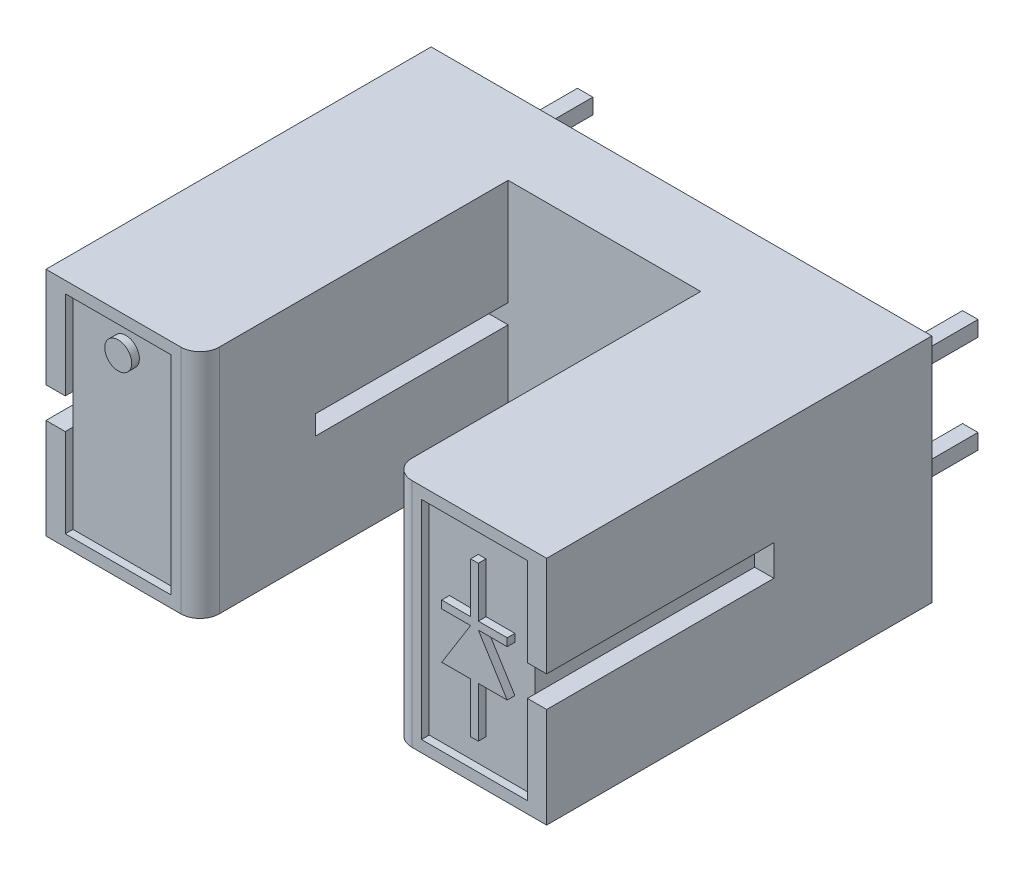
SolidWorks part; units mm, degrees
ref_plane "Front" through (0, 0, 0) normal (0, 0, 1) x (1, 0, 0)
ref_plane "Top" through (0, 0, 0) normal (0, 1, 0) x (1, 0, 0)
ref_plane "Right" through (0, 0, 0) normal (1, 0, 0) x (0, 0, -1)
sketch "Эскиз1" plane through (0, 0, 0) normal (0, 1, 0) x (1, 0, 0)
  line L0 (6.5, 0) -> (-6.5, 0)
  line L1 (6.5, 0) -> (6.5, -10)
  line L2 (6.5, -10) -> (2.5, -10)
  line L3 (2.5, -10) -> (2.5, -2)
  line L4 (2.5, -2) -> (-2.5, -2)
  line L5 (-2.5, -2) -> (-2.5, -10)
  line L6 (-2.5, -10) -> (-6.5, -10)
  line L8 (-6.5, 0) -> (-6.5, -10)
  line L9 (0, 0) -> (0, -2) construction
  dimension "D1" = 13
  dimension "D2" = 10
  dimension "D3" = 5
  dimension "D4" = 2
extrude "Бобышка-Вытянуть1" add sketch "Эскиз1" along normal blind 3 and the other way blind 3
fillet "Скругление1" radius 0.5 2 edges at (2.5, 0, 10) (-2.5, 0, 10)
sketch "Эскиз3" plane through (6.5, 0, 0) normal (1, 0, 0) x (0, 0, -1)
  line L0 (-10, -3) -> (-10, 3) construction
  line L1 (-10, -0.4) -> (-4.1, -0.4)
  line L2 (-10, -0.4) -> (-10, 0.4)
  line L3 (-10, 0.4) -> (-4.1, 0.4)
  line L4 (-4.1, -0.4) -> (-4.1, 0.4)
  line L5 (-10, -0.4) -> (-4.1, 0.4) construction
  line L6 (-10, 0.4) -> (-4.1, -0.4) construction
  line L7 (-10, 0) -> (-7.05, 0) construction
  point P4 (-7.05, 0)
  dimension "D1" = 0.8
  dimension "D2" = 5.9
extrude "Вырез-Вытянуть1" cut sketch "Эскиз3" against normal blind 0.5 contours L3 L4 L1 L2
sketch "Эскиз4" plane through (2.5, 0, 0) normal (-1, 0, 0) x (0, 0, 1)
  line L1 (2, 0.25) -> (7, 0.25)
  line L2 (2, 0.25) -> (2, -0.25)
  line L3 (2, -0.25) -> (7, -0.25)
  line L4 (7, 0.25) -> (7, -0.25)
  line L5 (2, 0.25) -> (7, -0.25) construction
  line L6 (2, -0.25) -> (7, 0.25) construction
  line L7 (0, 0) -> (4.5, 0) construction
  line L8 (2, -3) -> (2, 3) construction
  point P4 (4.5, 0)
  dimension "D1" = 0.5
  dimension "D2" = 5
extrude "Вырез-Вытянуть2" cut sketch "Эскиз4" against normal blind 0.5
mirror "Зеркальное отражение1" about plane through (0, 0, 0) normal (1, 0, 0) of "Вырез-Вытянуть2", "Вырез-Вытянуть1"
sketch "Эскиз5" plane through (0, 0, 10) normal (0, 0, 1) x (1, 0, 0)
  line L0 (-6, -0.4) -> (-6, 0.4) construction
  line L1 (-6, -2.7) -> (-3.25, -2.7)
  line L2 (-6, -2.7) -> (-6, 2.7)
  line L3 (-6, 2.7) -> (-3.25, 2.7)
  line L4 (-3.25, -2.7) -> (-3.25, 2.7)
  line L5 (-6, -2.7) -> (-3.25, 2.7) construction
  line L6 (-6, 2.7) -> (-3.25, -2.7) construction
  line L7 (0, 0) -> (-4.625, 0) construction
  line L8 (-6.5, -3) -> (-3, -3) construction
  line L9 (-2.5, 3) -> (-2.5, -3) construction
  line L10 (0, 0) -> (0, -3.5451) construction
  line L11 (3.25, -2.7) -> (3.25, 2.7)
  line L12 (6, -2.7) -> (3.25, -2.7)
  line L13 (6, -2.7) -> (6, 2.7)
  line L14 (6, 2.7) -> (3.25, 2.7)
  point P4 (-4.625, 0)
  dimension "D1" = 0.3
  dimension "D2" = 0.75
extrude "Вырез-Вытянуть3" cut sketch "Эскиз5" against normal blind 0.2
sketch "Эскиз6" plane through (0, 0, 9.8) normal (0, 0, 1) x (1, 0, 0)
  line L0 (-6, 2) -> (-3.25, 2) construction
  line L1 (-6, 2.7) -> (-6, 0.4) construction
  line L2 (-3.25, -2.7) -> (-3.25, 2.7) construction
  line L3 (4.725, -2) -> (4.725, -0.7)
  line L4 (4.725, -0.7) -> (5.475, -0.7)
  line L5 (5.475, -0.7) -> (4.725, 0.5)
  line L6 (4.725, 0.5) -> (5.475, 0.5)
  line L7 (5.475, 0.5) -> (5.475, 0.7)
  line L8 (5.475, 0.7) -> (4.725, 0.7)
  line L9 (4.725, 0.7) -> (4.725, 2)
  line L10 (4.725, -2) -> (4.525, -2)
  line L11 (4.625, -2) -> (4.625, 2) construction
  line L12 (4.525, 2) -> (4.725, 2)
  line L13 (4.525, 0.7) -> (4.525, 2)
  line L14 (3.775, 0.7) -> (4.525, 0.7)
  line L15 (3.775, 0.5) -> (3.775, 0.7)
  line L16 (4.525, 0.5) -> (3.775, 0.5)
  line L17 (3.775, -0.7) -> (4.525, 0.5)
  line L18 (4.525, -0.7) -> (3.775, -0.7)
  line L19 (4.525, -2) -> (4.525, -0.7)
  line L20 (3.25, 0) -> (6, 0) construction
  line L21 (3.25, 2.7) -> (3.25, -2.7) construction
  line L22 (6, 0.4) -> (6, -0.4) construction
  line L24 (6, 2.7) -> (3.25, 2.7) construction
  circle A0 centre (-4.625, 2) radius 0.35
  point P9 (-4.625, 2)
  point P10 (0, 0)
  point P35 (4.625, 0)
  point P36 (4.625, 0)
  dimension "D1" = 0.7
  dimension "D3" = 0.2
  dimension "D2" = 2
  dimension "D4" = 0.2
  dimension "D5" = 1.3
  dimension "D6" = 1.7
  dimension "D7" = 0.7
extrude "Бобышка-Вытянуть3" add sketch "Эскиз6" along normal up to surface (0.2 mm away) up to face at (5.2083, 0, 10)
sketch "Эскиз2" plane through (0, 0, 0) normal (0, 0, -1) x (-1, 0, 0)
  line L0 (4.8, 1.07) -> (5.2, 1.07)
  line L1 (-5.2, 1.47) -> (-4.8, 1.47)
  line L2 (-5.2, 1.47) -> (-5.2, 1.07)
  line L3 (-5.2, 1.07) -> (-4.8, 1.07)
  line L4 (-4.8, 1.47) -> (-4.8, 1.07)
  line L5 (-5.2, 1.47) -> (-4.8, 1.07) construction
  line L6 (-5.2, 1.07) -> (-4.8, 1.47) construction
  line L7 (5.2, 1.47) -> (5.2, 1.07)
  line L8 (4.8, 1.47) -> (5.2, 1.47)
  line L9 (4.8, 1.47) -> (4.8, 1.07)
  line L10 (4.8, -1.47) -> (5.2, -1.47)
  line L11 (5.2, -1.07) -> (5.2, -1.47)
  line L12 (4.8, -1.07) -> (5.2, -1.07)
  line L13 (4.8, -1.07) -> (4.8, -1.47)
  line L14 (-5.2, -1.47) -> (-4.8, -1.47)
  line L15 (-4.8, -1.07) -> (-4.8, -1.47)
  line L16 (-5.2, -1.07) -> (-4.8, -1.07)
  line L17 (-5.2, -1.07) -> (-5.2, -1.47)
  point P4 (-5, 1.27)
  dimension "D1" = 0.4
  dimension "D2" = 5
  dimension "D3" = 1.27
  dimension "D4" = 2
  dimension "D5" = 2
extrude "Бобышка-Вытянуть2" add sketch "Эскиз2" along normal blind 2.5
